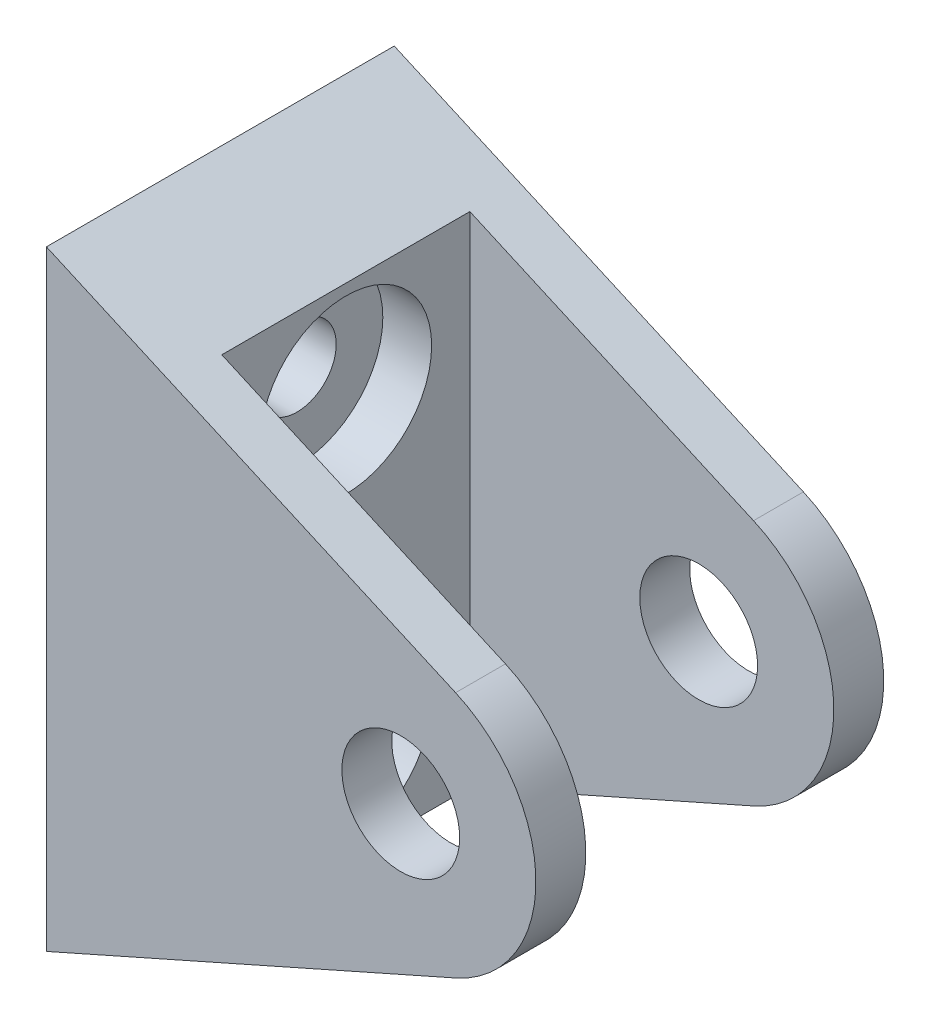
SolidWorks part; units mm, degrees
material "6061-T6 (SS)"
ref_plane "Front Plane" through (0, 0, 0) normal (0, 0, 1) x (1, 0, 0)
ref_plane "Top Plane" through (0, 0, 0) normal (0, 1, 0) x (1, 0, 0)
ref_plane "Right Plane" through (0, 0, 0) normal (1, 0, 0) x (0, 0, -1)
sketch "Sketch1" plane through (0, 0, 0) normal (0, 1, 0) x (1, 0, 0)
  line L0 (0, 0) -> (42.1978, 0)
  line L1 (42.1978, 0) -> (42.1978, 4.1529)
  line L2 (42.1978, 4.1529) -> (10.4478, 4.1529)
  line L3 (10.4478, 4.1529) -> (10.4478, 24.8031)
  line L4 (10.4478, 24.8031) -> (42.1978, 24.8031)
  line L5 (42.1978, 24.8031) -> (42.1978, 28.956)
  line L6 (42.1978, 28.956) -> (0, 28.956)
  line L7 (0, 28.956) -> (0, 0)
  line L8 (29.4978, 28.956) -> (29.4978, 0) construction
  circle A0 centre (29.4978, 14.478) radius 10.3505 construction
  dimension "D4" = 20.701
  dimension "D1" = 28.956
  dimension "D2" = 31.75
  dimension "D3" = 20.6502
  dimension "D5" = 12.7
extrude "Camber Block Extrude" add sketch "Sketch1" along normal blind 50.8
sketch "Sketch2" plane through (10.4478, 0, 0) normal (1, 0, 0) x (0, 0, -1)
  line L0 (4.1529, 25.4) -> (24.8031, 25.4) construction
  line L1 (4.1529, 50.8) -> (4.1529, 0) construction
  line L2 (24.8031, 50.8) -> (24.8031, 0) construction
  line L3 (14.478, 38.1) -> (14.478, 12.7) construction
  circle A0 centre (14.478, 38.1) radius 3.175 construction
  circle A1 centre (14.478, 12.7) radius 3.175 construction
  point P6 (14.478, 38.1)
  point P7 (14.478, 12.7)
  point P10 (14.478, 25.4)
  point P12 (14.478, 25.4)
  point P17 (14.478, 38.1)
  point P19 (14.478, 12.7)
  dimension "D2" = 6.35
  dimension "D3" = 6.35
  dimension "D1" = 25.4
hole_wizard "CBORE for 1/4 Binding Head Machine Screw1" positions "Sketch2" profile "Sketch3" counterbore size "1/4" standard "ANSI Inch" end condition through all
sketch "Sketch3" plane through (10.4478, 12.7, -14.478) normal (0, 1, 0) x (0, 0, -1)
  line L0 (0, 0) -> (0, 10.4478)
  line L1 (0, 10.4478) -> (3.2639, 10.4478)
  line L3 (3.2639, 10.4478) -> (3.2639, 4.064)
  line L4 (3.2639, 4.064) -> (7.1437, 4.064)
  line L5 (7.1437, 4.064) -> (7.1437, 0)
  line L7 (7.1437, 0) -> (0, 0)
  line L11 (0, -6.35) -> (0, 107.95) construction
  dimension "Thru Hole Dia." = 6.5278
  dimension "Thru Hole Depth" = 10.4478
  dimension "C'Bore Dia." = 14.2875
  dimension "C'Bore Depth" = 4.064
sketch "Sketch5" plane through (0, 0, 0) normal (0, 0, 1) x (1, 0, 0)
  line L0 (0, 25.4) -> (42.1978, 25.4) construction
  line L1 (0, 50.8) -> (0, 0) construction
  line L2 (42.1978, 50.8) -> (42.1978, 0) construction
  line L3 (0, 0) -> (34.0618, 15.115)
  line L4 (0, 50.8) -> (34.0618, 35.685)
  line L5 (0, 0) -> (42.1978, 0)
  line L6 (42.1978, 0) -> (42.1978, 50.8)
  line L7 (42.1978, 50.8) -> (0, 50.8)
  circle A0 centre (29.4978, 25.4) radius 4.9022
  arc A1 (34.0618, 15.115) -> (34.0618, 35.685) centre (29.4978, 25.4) ccw
  dimension "D1" = 9.8044
  dimension "D2" = 6.35
extrude "3/8 Clearance Close Fit" cut sketch "Sketch5" against normal up to surface (28.956 mm away) up to face at (21.0989, 25.4, -28.956)
